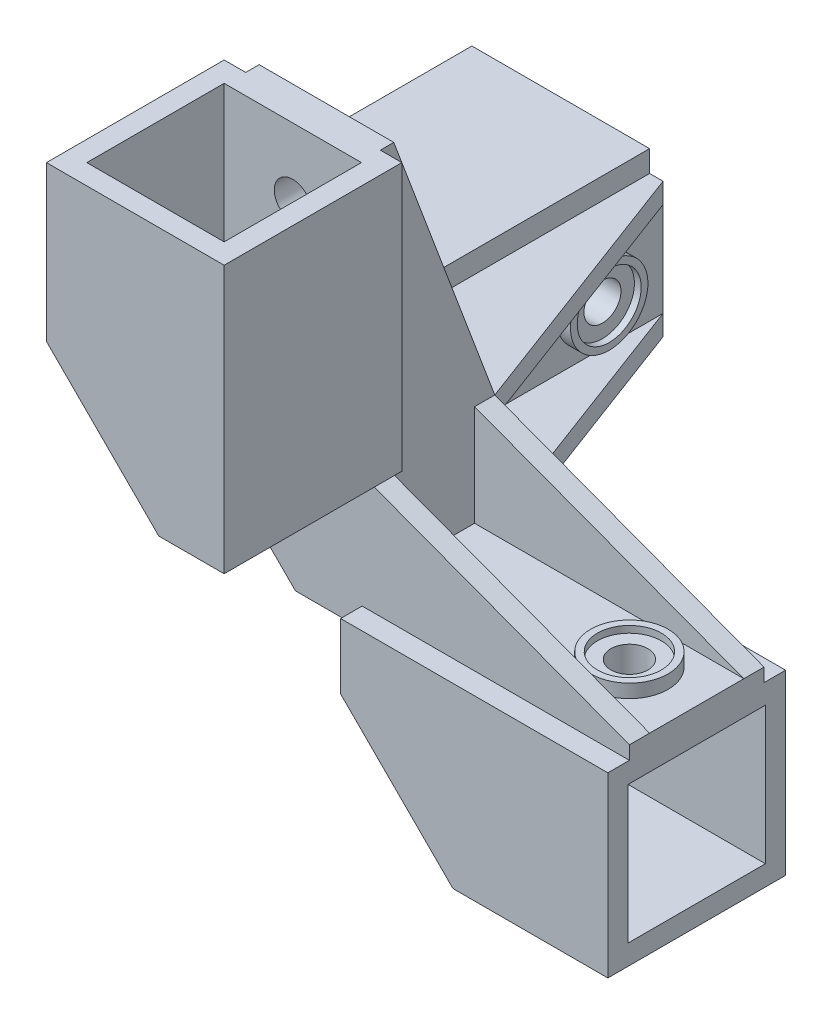
SolidWorks part; units mm, degrees
note: '?' marks a value the reader was unsure of. The reader was unsure of these and kept them because the rebuilt part matched: shared geometry of "Sketch3<2>", "Sketch4<3>", "Sketch4<4>".
ref_plane "Front Plane" through (0, 0, 0) normal (0, 0, 1) x (1, 0, 0)
ref_plane "Top Plane" through (0, 0, 0) normal (0, 1, 0) x (1, 0, 0)
ref_plane "Right Plane" through (0, 0, 0) normal (1, 0, 0) x (0, 0, -1)
sketch "Sketch1" plane through (0, 0, 0) normal (0, 1, 0) x (1, 0, 0)
  line L1 (0, 0) -> (20, 0)
  line L2 (0, 0) -> (0, 20)
  line L3 (0, 20) -> (20, 20)
  line L4 (20, 0) -> (20, 20)
  dimension "D1" = 20
  dimension "D2" = 20
extrude "Boss-Extrude1" add sketch "Sketch1" along normal blind 20
sketch "Sketch2" plane through (0, 0, 0) normal (0, 1, 0) x (1, 0, 0)
  line L1 (20, 0) -> (60, 0)
  line L2 (20, 0) -> (20, 20)
  line L3 (20, 20) -> (60, 20)
  line L4 (60, 0) -> (60, 20)
  dimension "D1" = 20
  dimension "D2" = 40
extrude "Boss-Extrude2" add sketch "Sketch2" along normal blind 5
sketch "Sketch3" plane through (0, 0, 0) normal (0, 0, 1) x (1, 0, 0)
  line L0 (20, 5) -> (20, 20)
  line L1 (20, 20) -> (60, 5)
  line L2 (60, 5) -> (20, 5)
extrude "Boss-Extrude3" add sketch "Sketch3" against normal blind 3
extrude "Boss-Extrude4" add sketch "Sketch3<2>" along normal blind 3 from offset 20 offset against normal yes
sketch "Sketch3<2>" plane through (0, 0, 0) normal (0, 0, 1) x (1, 0, 0) same geometry as "Sketch3"
sketch "Sketch4" plane through (0, 5, 0) normal (0, 1, 0) x (1, 0, 0)
  line L0 (60, 10) -> (50, 10)
  line L1 (60, 3) -> (60, 17) construction
  circle A0 centre (50, 10) radius 2.75
  circle A1 centre (50, 10) radius 4.75
  circle A2 centre (50, 10) radius 5.75
  dimension "D1" = 5.5
  dimension "D2" = 9.5
  dimension "D3" = 1
  dimension "D4" = 10
extrude "Boss-Extrude5" add sketch "Sketch4" along normal blind 1
extrude "Cut-Extrude1" cut sketch "Sketch4<3>" against normal through all
sketch "Sketch4<3>" plane through (0, 5, 0) normal (0, 1, 0) x (1, 0, 0) same geometry as "Sketch4"
extrude "Boss-Extrude6" add sketch "Sketch4<4>" along normal blind 2
sketch "Sketch4<4>" plane through (0, 5, 0) normal (0, 1, 0) x (1, 0, 0) same geometry as "Sketch4"
ref_axis "Axis1" through (20, 20, -20) along (-0.5774, -0.5774, 0.5774)?
sketch "Sketch5" plane through (0, 0, 0) normal (-1, 0, 0) x (0, 0, 1)
  line L0 (-20.2, 0) -> (0.2, 0)
  line L1 (-20, -0.2) -> (0, -0.2)
  line L2 (-20, -0.2) -> (-20, -20.2)
  line L3 (-20, -20.2) -> (0, -20.2)
  line L4 (0, -0.2) -> (0, -20.2)
  line L5 (0.2, 0) -> (0.2, -20.4)
  line L6 (-20.2, -20.4) -> (0.2, -20.4)
  line L7 (-20.2, 0) -> (-20.2, -20.4)
  line L8 (0, -0.2) -> (0, 0) construction
  line L9 (-20, 0) -> (0, 0) construction
  line L10 (-23.2, 3) -> (3.2, 3)
  line L11 (3.2, 3) -> (3.2, -23.4)
  line L12 (-23.2, -23.4) -> (3.2, -23.4)
  line L13 (-23.2, 3) -> (-23.2, -23.4)
  line M9 (0, 0) -> (0, 20)
  line M11 (-20, 20) -> (-20, 0)
  dimension "D1" = 20
  dimension "D2" = 0.2
  dimension "D3" = 3
extrude "Boss-Extrude7" add sketch "Sketch5" against normal blind 39.7 from offset 20.3 contours L10 L13 L12 L11 L0 L5 L6 L7 M9 M11 offset against normal yes
pattern_circular "CirPattern1" count 3 every 120 about axis through (0, 0, 0) along (0.5774, 0.5774, -0.5774) of "Boss-Extrude2", "Boss-Extrude4", "Boss-Extrude5", "Boss-Extrude6", "Cut-Extrude1", "Boss-Extrude3", "Boss-Extrude7"
ref_plane "Plane1" through (0, 0, 0) normal (-0.5774, -0.5774, 0.5774) x (0.8165, -0.4082, 0.4082)
ref_plane "Plane2" through (3.4641, 3.4641, -3.4641) normal (-0.5774, -0.5774, 0.5774) x (0.8165, -0.4082, 0.4082)
other "SurfaceCut1" flip cut yes
